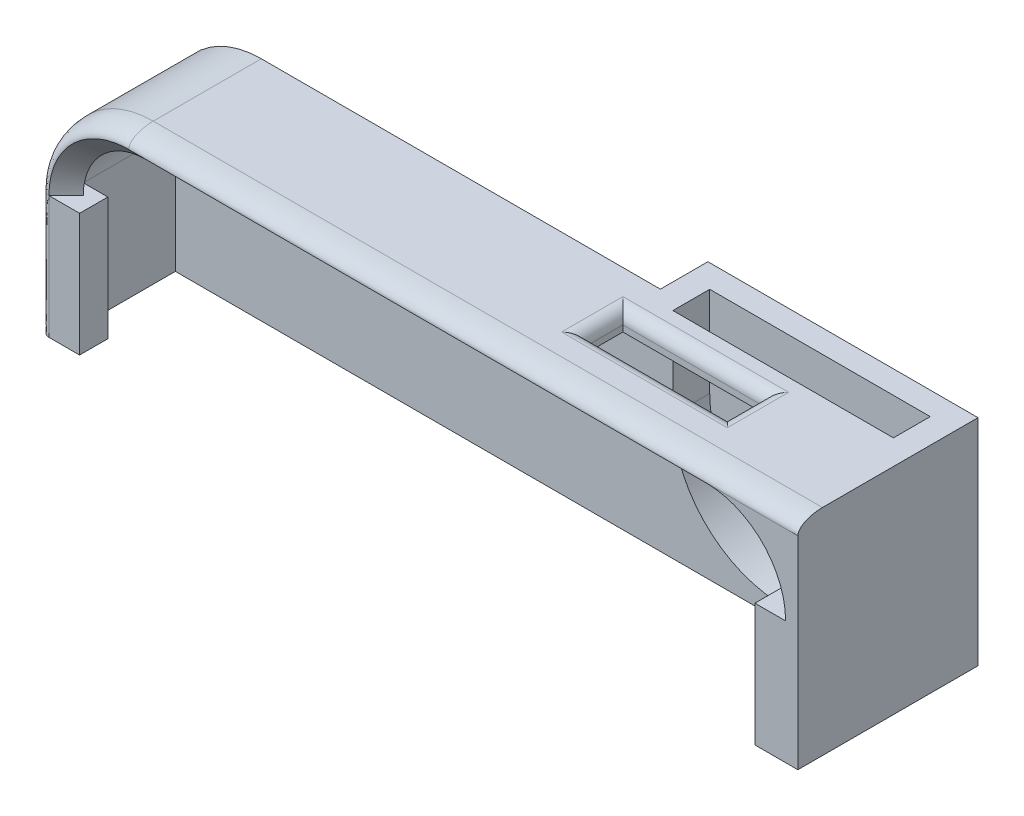
SolidWorks part; units mm, degrees
ref_plane "Front Plane" through (0, 0, 0) normal (0, 0, 1) x (1, 0, 0)
ref_plane "Top Plane" through (0, 0, 0) normal (0, 1, 0) x (1, 0, 0)
ref_plane "Right Plane" through (0, 0, 0) normal (1, 0, 0) x (0, 0, -1)
sketch "Sketch1" plane through (0, 0, 0) normal (0, 0, 1) x (1, 0, 0)
  line L0 (31, 17.5) -> (31, 0)
  line L1 (0, 0) -> (62, 0)
  line L2 (0, 0) -> (0, 10)
  line L3 (7.5, 17.5) -> (54.5, 17.5)
  line L4 (62, 0) -> (62, 10)
  line L5 (7.5, 16) -> (54.5, 16)
  line L6 (62, 10) -> (62, 17.5)
  line L7 (62, 17.5) -> (54.5, 17.5)
  line L9 (1.5, 0) -> (1.5, 10)
  line L12 (60.5, 10) -> (60.5, 0)
  arc A0 (0, 10) -> (7.5, 17.5) centre (7.5, 10) cw
  arc A2 (1.5, 10) -> (7.5, 16) centre (7.5, 10) cw
  arc A3 (60.5, 10) -> (54.5, 16) centre (54.5, 10) ccw
  dimension "D5" = 1.5
extrude "Boss-Extrude1" add sketch "Sketch1" along normal blind 10.8 contours L9 A2 L5 L0 L3 A0 L2 L1 | A3 L12 L1 L4 L3 L0 L5 region at (42.75, 17.144, 0) region at (30.644, 16.75, 0)
sketch "Sketch2" plane through (0, 0, 0) normal (0, 0, -1) x (-1, 0, 0)
  line L0 (-1.5, 0) -> (-1.5, 10)
  line L1 (-7.5, 16) -> (-54.5, 16)
  line L2 (-60.5, 0) -> (-60.5, 10)
  line L3 (-60.5, 0) -> (-1.5, 0)
  arc A0 (-1.5, 10) -> (-7.5, 16) centre (-7.5, 10) ccw
  arc A1 (-54.5, 16) -> (-60.5, 10) centre (-54.5, 10) ccw
extrude "Boss-Extrude2" add sketch "Sketch2" against normal blind 1 separate body
combine bodies "Combine1" operation type add bodies to combine 102 101
sketch "Sketch3" plane through (0, 0, 10.8) normal (0, 0, 1) x (1, 0, 0)
  line L0 (0, 0) -> (3.5, 0)
  line L1 (0, 0) -> (0, 10)
  line L2 (0, 0) -> (0, 10) construction
  line L3 (3.5, 0) -> (3.5, 10)
  line L4 (3.5, 10) -> (0, 10)
  line L5 (1.5, 10) -> (1.5, 0)
  line L6 (31, 16) -> (31, -7.5027)
  line L7 (7.5, 16) -> (54.5, 16) construction
  line L8 (60.5, 10) -> (60.5, 0)
  line L9 (62, 0) -> (58.5, 0)
  line L10 (58.5, 10) -> (62, 10)
  line L11 (58.5, 0) -> (58.5, 10)
  line M7 (1.5, 0) -> (1.5, 10)
  line M11 (60.5, 10) -> (60.5, 0)
  dimension "D1" = 3.5
  dimension "D2" = 10
extrude "Boss-Extrude3" add sketch "Sketch3" against normal blind 2.3 contours L3 L4 L0 M7 | L11 L9 L10 M11 region at (2.5, 5, 10.8) region at (59.5, 5, 10.8)
fillet "Fillet1" radius 1 3 edges at (0, 5, 10.8) (2.1967, 15.3033, 10.8) (34.75, 17.5, 10.8) second distance 2 first distance on face at (29.0728, 9.3107, 10.8)
sketch "Sketch4" plane through (0, 17.5, 0) normal (0, 1, 0) x (1, 0, 0)
  line L1 (51.5, -6.05) -> (40, -6.05)
  line L2 (51.5, -6.05) -> (51.5, -3.05)
  line L3 (51.5, -3.05) -> (40, -3.05)
  line L4 (40, -6.05) -> (40, -3.05)
  line L5 (7.5, 0) -> (62, 0) construction
  dimension "D2" = 11.5
  dimension "D3" = 3.05
  dimension "D4" = 3
extrude "Cut-Extrude1" cut sketch "Sketch4" against normal up to next
sketch "Sketch5" plane through (0, 0, 10.8) normal (0, 0, 1) x (1, 0, 0)
  line L0 (31, 16) -> (31, -4.8703) construction
  line L1 (60.5, 10) -> (59.5, 10)
  line L3 (54.5, 15) -> (7.5, 15)
  line L4 (3.5, 10) -> (1.5, 10) construction
  line L8 (54.5, 16) -> (7.5, 16)
  line L9 (1.5, 10) -> (2.5, 10)
  arc A0 (59.5, 10) -> (54.5, 15) centre (54.5, 10) ccw
  arc A1 (2.5, 10) -> (7.5, 15) centre (7.5, 10) cw
  arc A3 (60.5, 10) -> (54.5, 16) centre (54.5, 10) ccw
  arc A4 (7.5, 16) -> (1.5, 10) centre (7.5, 10) ccw
extrude "Boss-Extrude4" add sketch "Sketch5" against normal blind 2.3
chamfer "Chamfer1" distance 1.5 angle 45 3 edges at (3.9645, 13.5355, 10.8) (58.0355, 13.5355, 10.8) (31, 15, 10.8)
chamfer "Chamfer3" distance 1 angle 45 3 edges at (3.9645, 13.5355, 8.5) (58.0355, 13.5355, 8.5) (31, 15, 8.5)
sketch "Sketch6" plane through (0, 0, 0) normal (0, 0, -1) x (-1, 0, 0)
  line L0 (-59.98, 10.15) -> (-59.98, 16.85)
  line L2 (-42.02, 10.15) -> (-42.02, 16.85)
  line L3 (-59.98, 10.15) -> (-42.02, 10.15) construction
  line L4 (-42.02, 16.85) -> (-42.02, 17.5)
  line L5 (-7.5, 17.5) -> (-62, 17.5) construction
  line L6 (-42.02, 17.5) -> (-59.98, 17.5)
  line L7 (-59.98, 17.5) -> (-59.98, 16.85)
  arc A0 (-59.98, 10.15) -> (-42.02, 10.15) centre (-51, 10.15) ccw
  dimension "D1" = 7.35
extrude "Cut-Extrude2" cut sketch "Sketch6" against normal blind 2
sketch "Sketch9" plane through (0, 0, 0) normal (0, 0, -1) x (-1, 0, 0)
  line L0 (-54.5, 0) -> (-62, 0)
  line L1 (-62, 0) -> (-62, 6.85)
  line L2 (-7.5, 17.5) -> (-42.02, 17.5) construction
  line L3 (-40, 6.8545) -> (-40, 0)
  line L4 (-54.5, 0) -> (-47.2921, 0)
  line L5 (-62, 0) -> (0, 0) construction
  line L6 (-40, 0) -> (-47.2921, 0)
  line L9 (-62, 17.5) -> (-59.98, 17.5)
  line L10 (-59.98, 17.5) -> (-59.98, 10.15)
  line L11 (-62, 6.85) -> (-62, 17.5)
  line L13 (-40, 17.5) -> (-40, 6.8545)
  line L14 (-42.02, 17.5) -> (-40, 17.5)
  line L15 (-42.02, 10.15) -> (-42.02, 17.5)
  arc A4 (-59.98, 10.15) -> (-42.02, 10.15) centre (-51, 10.15) ccw
extrude "Boss-Extrude6" add sketch "Sketch9" along normal blind 2
fillet "Fillet2" radius 1 4 edges at (45.75, 17.5, 3.05) (51.5, 17.5, 4.55) (45.75, 17.5, 6.05) (40, 17.5, 4.55)
sketch "Sketch48" plane through (0, 0, 2) normal (0, 0, -1) x (-1, 0, 0)
  line L4 (-54.5, 16) -> (-42.02, 16)
  line L5 (-42.02, 16) -> (-42.02, 17.5)
  line L6 (-42.02, 17.5) -> (-59.98, 17.5)
  line L7 (-59.98, 17.5) -> (-59.98, 12.4433)
  line L8 (-54.5, 16) -> (-42.02, 16)
  line L9 (-42.02, 16) -> (-42.02, 17.5)
  line L10 (-42.02, 17.5) -> (-59.98, 17.5)
  line L11 (-59.98, 17.5) -> (-59.98, 12.4433)
  arc A1 (-54.5, 16) -> (-59.98, 12.4433) centre (-54.5, 10) ccw
  arc A2 (-54.5, 16) -> (-59.98, 12.4433) centre (-54.5, 10) ccw
  dimension "D1" = 0
extrude "Boss-Extrude36" add sketch "Sketch48" along normal up to surface (1 mm away) up to face at (37.154, 8.5593, 1)
sketch "Sketch10" plane through (0, 0, -2) normal (0, 0, -1) x (-1, 0, 0)
  line L0 (-54.5, 0) -> (-62, 0)
  line L1 (-62, 0) -> (-62, 3.4)
  line L2 (-40, 17.5) -> (-40, 6.8545)
  line L3 (-54.5, 0) -> (-47.2921, 0)
  line L4 (-40, 6.8545) -> (-40, 0)
  line L5 (-62, 17.5) -> (-40, 17.5)
  line L6 (-40, 0) -> (-47.2921, 0)
  line L8 (-62, 3.4) -> (-62, 17.5)
extrude "Boss-Extrude7" add sketch "Sketch10" along normal blind 1.87
sketch "Sketch11" plane through (0, 0, -2) normal (0, 0, 1) x (1, 0, 0)
  circle A0 centre (51, 8.65) radius 2.5
  dimension "D1" = 5
extrude "Cut-Extrude3" cut sketch "Sketch11" against normal through all
